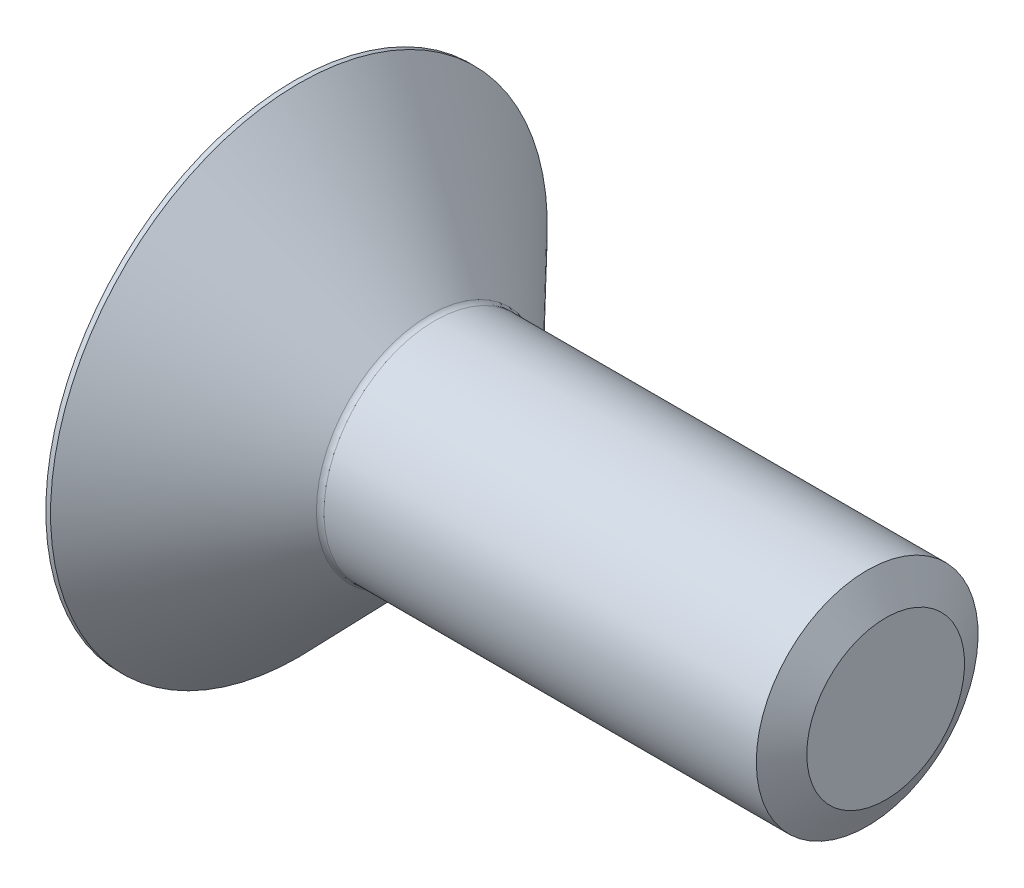
SolidWorks part; units mm, degrees
material "8.8级"
ref_plane "前视基准面" through (0, 0, 0) normal (0, 0, 1) x (1, 0, 0)
ref_plane "上视基准面" through (0, 0, 0) normal (0, 1, 0) x (1, 0, 0)
ref_plane "右视基准面" through (0, 0, 0) normal (1, 0, 0) x (0, 0, -1)
sketch "草图1" plane through (0, 0, 0) normal (0, 0, 1) x (1, 0, 0)
  line L0 (0, 1.5) -> (-6.0976, 1.5)
  line L1 (-6.1695, 1.5305) -> (-7.9362, 3.36)
  line L2 (-7.9362, 3.36) -> (-8, 3.36)
  line L3 (-8, 3.36) -> (-8, 0)
  line L4 (-8, 0) -> (0, 0)
  line L5 (0, 0) -> (0, 1.5)
  line L6 (0, 0) -> (-8, 0) construction
  arc A0 (-6.0976, 1.5) -> (-6.1695, 1.5305) centre (-6.0976, 1.6) cw
  point P9 (-6.14, 1.5)
  dimension "r" = 0.1
  dimension "k" = 1.86
  dimension "dk" = 6.72
  dimension "l" = 8
  dimension "d" = 3
  dimension "D5" = 46
revolve "旋转1" add sketch "草图1" angle 360 about L6
cosmetic thread "装饰螺纹线1" parameters "b"=6, "D2"=2.58
sketch "草图2" plane through (-8, 0, 0) normal (-1, 0, 0) x (0, 0, 1)
  line L1 (0, 1.1547) -> (-1, 0.5774)
  line L2 (-1, 0.5774) -> (-1, -0.5774)
  line L3 (-1, -0.5774) -> (0, -1.1547)
  line L4 (0, -1.1547) -> (1, -0.5774)
  line L5 (1, -0.5774) -> (1, 0.5774)
  line L6 (1, 0.5774) -> (0, 1.1547)
  circle A0 centre (0, 0) radius 1 construction
  dimension "s" = 2
extrude "切除-拉伸1" cut sketch "草图2" against normal blind 1.96
sketch "草图6" plane through (0, 0, 0) normal (0, 0, 1) x (1, 0, 0)
  line L0 (-6.9, 1.1547) -> (-6.2333, 0)
  line L1 (-6.2333, 0) -> (-5.74, 0)
  line L2 (-5.74, 0) -> (-5.74, 1.1547)
  line L3 (-5.74, 1.1547) -> (-6.9, 1.1547)
  line L4 (-8, 0) -> (-6.04, 0) construction
  line L5 (-8, 0) -> (-10.3, 0) construction
  dimension "t" = 1.1
  dimension "D1" = 60
  dimension "t1" = 1.96
  dimension "e-s" = 0.3
  dimension "e" = 2.3
revolve "旋转2" add sketch "草图6" angle 360 about L4
sketch "草图7" plane through (0, 0, 0) normal (0, 0, 1) x (1, 0, 0)
  line L0 (-8, 1.1547) -> (-8, 0)
  line L1 (-8, 0) -> (-7.67, 0)
  line L2 (-7.67, 0) -> (-8, 1.1547)
  line L3 (-8, 0) -> (-7.67, 0) construction
  dimension "e-s*1.1" = 0.33
revolve "切除-旋转2" cut sketch "草图7" angle 360 about L3
sketch "草图4" plane through (0, 0, 0) normal (0, 0, 1) x (1, 0, 0)
  line L0 (-0.25, 1.5) -> (0, 1.067)
  line L1 (0, -1.5) -> (0, 1.5) construction
  line L2 (0, 1.067) -> (0.25, 1.5)
  line L3 (0.25, 1.5) -> (-0.25, 1.5)
  line L4 (-0.25, 0) -> (0.25, 0) construction
  dimension "d" = 3
  dimension "p" = 0.5
revolve "切除-旋转1" cut sketch "草图4" angle 360 about L4
ref_axis "基准轴1" through (-21.1715, 0, 0) along (1, 0, 0)
pattern_linear "阵列(线性)2" [suppressed] count 12 spacing 0.5 along (-1, 0, 0) of bodies 104
equation "\"D2@装饰螺纹线1\" = \"d@草图1\" * 0.86"
equation "\"e-s@草图6\" = \"e@草图6\" - \"s@草图2\""
equation "\"t1@切除-拉伸1\" = \"k@草图1\" + 0.1"
equation "\"t1@草图6\" = \"t1@切除-拉伸1\""
equation "\"e-s*1.1@草图7\" = \"e-s@草图6\" * 1.1"
equation "\"d@草图4\" = \"d@草图1\""
equation "\"D3@阵列(线性)2\" = \"p@草图4\""
equation "\"D1@阵列(线性)2\" = \"b@装饰螺纹线1\" / \"p@草图4\""
